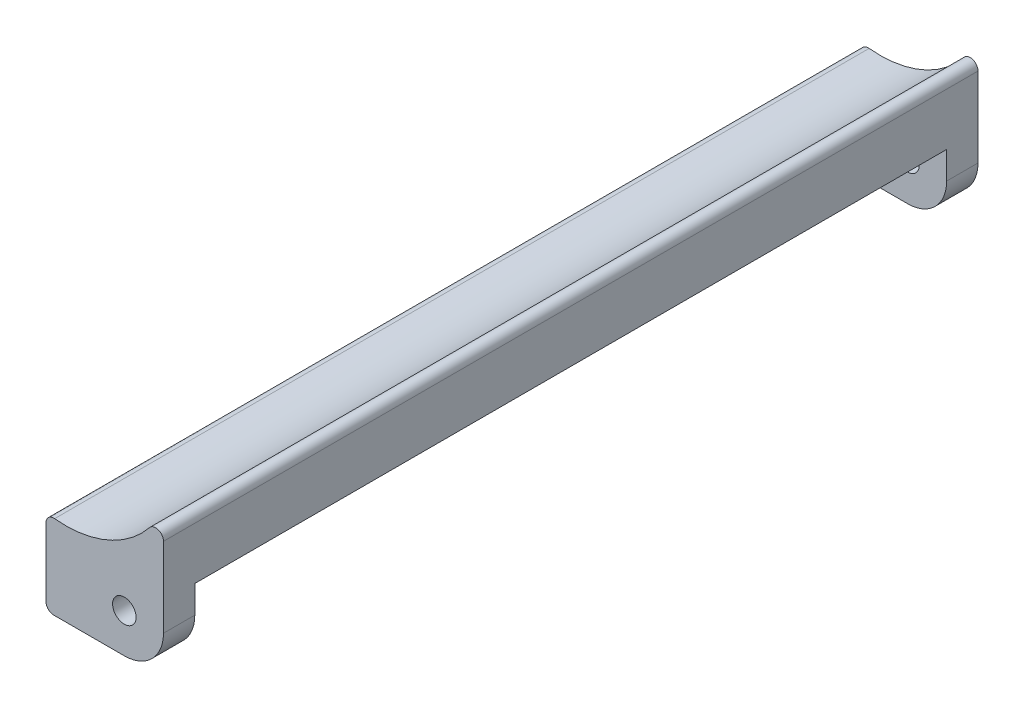
SolidWorks part; units mm, degrees
ref_plane "前视基准面" through (0, 0, 0) normal (0, 0, 1) x (1, 0, 0)
ref_plane "上视基准面" through (0, 0, 0) normal (0, 1, 0) x (1, 0, 0)
ref_plane "右视基准面" through (0, 0, 0) normal (1, 0, 0) x (0, 0, -1)
other "Configuration Table"
sketch "草图1" plane through (0, 0, 0) normal (0, 0, 1) x (1, 0, 0)
  line L0 (5.25, 13.9) -> (5.25, 0)
  line L1 (0, 0) -> (10.5, 0)
  line L2 (0, 0) -> (0, 13.9)
  line L3 (0, 13.9) -> (10.5, 13.9)
  line L4 (10.5, 0) -> (10.5, 13.9)
  line L5 (5.25, 13.9) -> (5.25, 28.2)
  line L6 (5.25, 28.2) -> (5.25, 32.1)
  line L7 (5.25, 6.95) -> (-1.6, 6.95)
  line L8 (5.25, 6.95) -> (17.8, 6.95)
  line L9 (-1.6, 7.5) -> (-1.6, 4.5)
  line L11 (-4.2, 4.5) -> (-4.2, 7.5)
  line L13 (14.7, 8.45) -> (14.7, 5.45)
  line L15 (12.1, 5.45) -> (12.1, 8.45)
  line L17 (5.25, 32.1) -> (5.25, 22.25)
  line L18 (5.25, 6.95) -> (-7.3, 6.95)
  line L19 (5.25, 32.1) -> (5.25, 41)
  line L20 (5.25, 41) -> (17.75, 41)
  line L21 (17.75, 41) -> (17.75, -19)
  line L22 (17.75, -19) -> (-7.25, -19)
  line L23 (-7.25, -19) -> (-7.25, 41)
  line L24 (-7.25, 41) -> (5.25, 41)
  line L25 (-7.25, 22.25) -> (17.75, 22.25)
  line L26 (-2.9, 8.8) -> (-2.9, 3.2)
  line L27 (-7.25, 41) -> (-28.25, 41)
  line L28 (-28.25, 41) -> (-28.25, -19)
  line L29 (-28.25, -19) -> (-7.25, -19)
  line L30 (5.25, 32.1) -> (17.75, 32.1)
  line L32 (-7.25, 32.1) -> (-0.3, 32.1)
  line L33 (2.75, -19) -> (2.75, -8.1208)
  line L38 (-28.25, 9.5) -> (-7.25, 9.5)
  line L39 (-21.75, 9.5) -> (-21.75, 18.5)
  line L52 (-21.75, 18.5) -> (-14.95, 18.5)
  line L54 (-24.75, -18.7697) -> (-24.75, -19)
  line L57 (-14.95, 18.5) -> (-14.95, 9.5)
  line L58 (-28.25, 23.1) -> (-7.25, 23.1)
  line L59 (-13.85, 17) -> (-13.85, 11)
  line L60 (-13.85, 11) -> (-11.85, 11)
  line L61 (-11.85, 11) -> (-11.85, 17)
  line L62 (-11.85, 17) -> (-13.85, 17)
  line L63 (-11.85, 14) -> (-13.85, 14)
  line L64 (-22.85, 17) -> (-22.85, 11)
  line L65 (-22.85, 11) -> (-24.85, 11)
  line L66 (-24.85, 11) -> (-24.85, 17)
  line L67 (-24.85, 17) -> (-22.85, 17)
  line L68 (-23.85, 14) -> (-24.0253, 14)
  line L69 (-14.95, 14) -> (-15.1329, 14)
  line L70 (-28.25, 26.1) -> (-18.25, 26.1)
  line L71 (17.75, 41) -> (28.0357, 41)
  line L73 (-28.25, 36.1) -> (-28.25, 26.1)
  line L74 (-28.25, 26.1) -> (-18.25, 26.1)
  line L76 (17.75, 41) -> (18.75, 41)
  line L77 (33.0357, 36) -> (33.0357, 26.1)
  line L78 (35.0357, -19) -> (17.75, -19)
  line L79 (9.25, -14) -> (9.25, -19)
  line L80 (12.75, -10.5) -> (17.75, -10.5)
  line L82 (17.75, 23.1) -> (30.0357, 23.1)
  line L87 (17.75, 26.1) -> (17.7271, 26.1)
  arc A0 (10.5, 8.65) -> (0, 8.65) centre (5.25, 8.65) ccw
  arc A1 (0, 5.25) -> (10.5, 5.25) centre (5.25, 5.25) ccw
  circle A3 centre (5.25, 32.1) radius 3.9
  circle A5 centre (5.25, 32.1) radius 5.55
  arc A6 (17.75, 14.2282) -> (-7.25, 14.2282) centre (5.25, 8.5) ccw
  arc A11 (-7.25, -0.3282) -> (17.75, -0.3282) centre (5.25, 5.4) ccw
  arc A12 (-1.6, 7.5) -> (-4.2, 7.5) centre (-2.9, 7.5) ccw
  arc A13 (-4.2, 4.5) -> (-1.6, 4.5) centre (-2.9, 4.5) ccw
  arc A15 (12.1, 5.45) -> (14.7, 5.45) centre (13.4, 5.45) ccw
  arc A16 (14.7, 8.45) -> (12.1, 8.45) centre (13.4, 8.45) ccw
  arc A28 (-28.25, -14) -> (-23.25, -19) centre (-23.25, -14) ccw
  arc A29 (-23.25, 41) -> (-28.25, 36) centre (-23.25, 36) ccw
  circle A33 centre (14.2, 32.1) radius 1.5
  circle A34 centre (-3.7, 32.1) radius 1.5
  arc A35 (-22.85, 16) -> (-24.85, 16) centre (-23.85, 16) ccw
  arc A37 (-24.85, 12) -> (-22.85, 12) centre (-23.85, 12) ccw
  arc A38 (-11.85, 16) -> (-13.85, 16) centre (-12.85, 16) ccw
  arc A39 (-13.85, 12) -> (-11.85, 12) centre (-12.85, 12) ccw
  arc A40 (-14.95, 15.1) -> (-21.75, 15.1) centre (-18.35, 15.1) ccw
  arc A41 (-21.75, 12.9) -> (-14.95, 12.9) centre (-18.35, 12.9) ccw
  circle A42 centre (-23.25, 31.1) radius 1.5
  arc A47 (33.0357, 36) -> (28.0357, 41) centre (28.0357, 36) ccw
  circle A49 centre (28.0357, 31.1) radius 1.5
  arc A50 (12.75, -19) -> (17.75, -14) centre (12.75, -14) ccw
  arc A51 (30.0357, 23.1) -> (33.0357, 26.1) centre (30.0357, 26.1) ccw
  circle A52 centre (-23.25, -14) radius 1.5
  circle A53 centre (-12.25, -14) radius 1.5
  circle A54 centre (-2.25, -14) radius 1.5
  circle A55 centre (12.75, -14) radius 1.5
  arc A56 (12.75, -10.5) -> (9.25, -14) centre (12.75, -14) ccw
  point P7 (5.25, 8.65)
  point P10 (5.25, 5.25)
  point P20 (0, 6.95)
  point P31 (15.55, 32.1)
  point P35 (5.25, 37.65)
  point P48 (10.8, 32.1)
  point P60 (12.7, 32.1)
  point P64 (15.7, 32.1)
  point P65 (-0.3, 32.1)
  point P71 (-14.95, 14)
  point P81 (-22.85, 14)
  point P86 (-23.85, 17)
  point P87 (-23.85, 11)
  point P90 (5.25, -8.35)
  point P96 (-12.85, 17)
  point P97 (-12.85, 11)
  point P104 (-18.35, 18.5)
  point P116 (-2.2, 32.1)
  point P117 (-5.2, 32.1)
  point P121 (-18.35, 9.5)
  point P127 (5.25, -19)
  point P131 (-18.35, 24.6)
  point P150 (33.0357, 33.1)
  point P154 (28.0357, 31.1)
  dimension "D6" = 3.9
  dimension "D15" = 15.3
  dimension "D13" = 11.1
  dimension "D21" = 5
  dimension "D22" = 27.5
  dimension "D23" = 27.5
  dimension "D37" = 23.6
  dimension "D14" = 8.95
  dimension "D33" = 17.9
  dimension "D39" = 3
  dimension "D43" = 3
  dimension "D47" = 3
  dimension "D49" = 3
  dimension "D51" = 5
  dimension "D48" = 3
  dimension "D50" = 3
  dimension "D58" = 3.5
  dimension "D1" = 10.5
  dimension "D2" = 13.9
  dimension "D3" = 5.25
  dimension "D4" = 5.25
  dimension "D5" = 14.3
  dimension "D7" = 1.6
  dimension "D8" = 51.1
  dimension "D9" = 46
  dimension "D10" = 8.95
  dimension "D11" = 1.6
  dimension "D12" = 12.55
  dimension "D16" = 12.55
  dimension "D17" = 10.65
  dimension "D18" = 60
  dimension "D19" = 12.5
  dimension "D20" = 12.5
  dimension "D24" = 28.5
  dimension "D25" = 9
  dimension "D26" = 6.8
  dimension "D27" = 2.05
  dimension "D28" = 6.5
  dimension "D29" = 4.5
  dimension "D30" = 25
  dimension "D31" = 3
  dimension "D32" = 2
  dimension "D34" = 3
  dimension "D35" = 1.1
  dimension "D36" = 2
  dimension "D38" = 2.05
  dimension "D40" = 3
  dimension "D41" = 1
  dimension "D42" = 1
  dimension "D44" = 7.5
  dimension "D45" = 8
  dimension "D46" = 5
  dimension "D52" = 5
  dimension "D53" = 5
  dimension "D54" = 5
  dimension "D55" = 5
  dimension "D56" = 5
  dimension "D57" = 5
extrude "凸台-拉伸1" add sketch "草图1" along normal blind 104 contours A56 L80 L21 A11 L33 L22 L79 region at (9.344, -11.1653, 0)
extrude "凸台-拉伸2" add sketch "草图1<23>" along normal blind 4 contours L80 A56 L79 L22 A50 L21 A55 region at (17.6298, -12.25, 0)
sketch "草图1<23>" plane through (0, 0, 0) normal (0, 0, 1) x (1, 0, 0) same geometry as "草图1"
extrude "凸台-拉伸3" add sketch "草图1<24>" along normal blind 4 from offset 100 contours L80 A56 L79 L22 A50 L21 A55 region at (17.6298, -12.25, 0)
sketch "草图1<24>" plane through (0, 0, 0) normal (0, 0, 1) x (1, 0, 0) same geometry as "草图1"
fillet "圆角1" radius 1 3 edges at (2.75, -8.1208, 52) (2.75, -19, 52) (17.75, -0.3282, 52)
